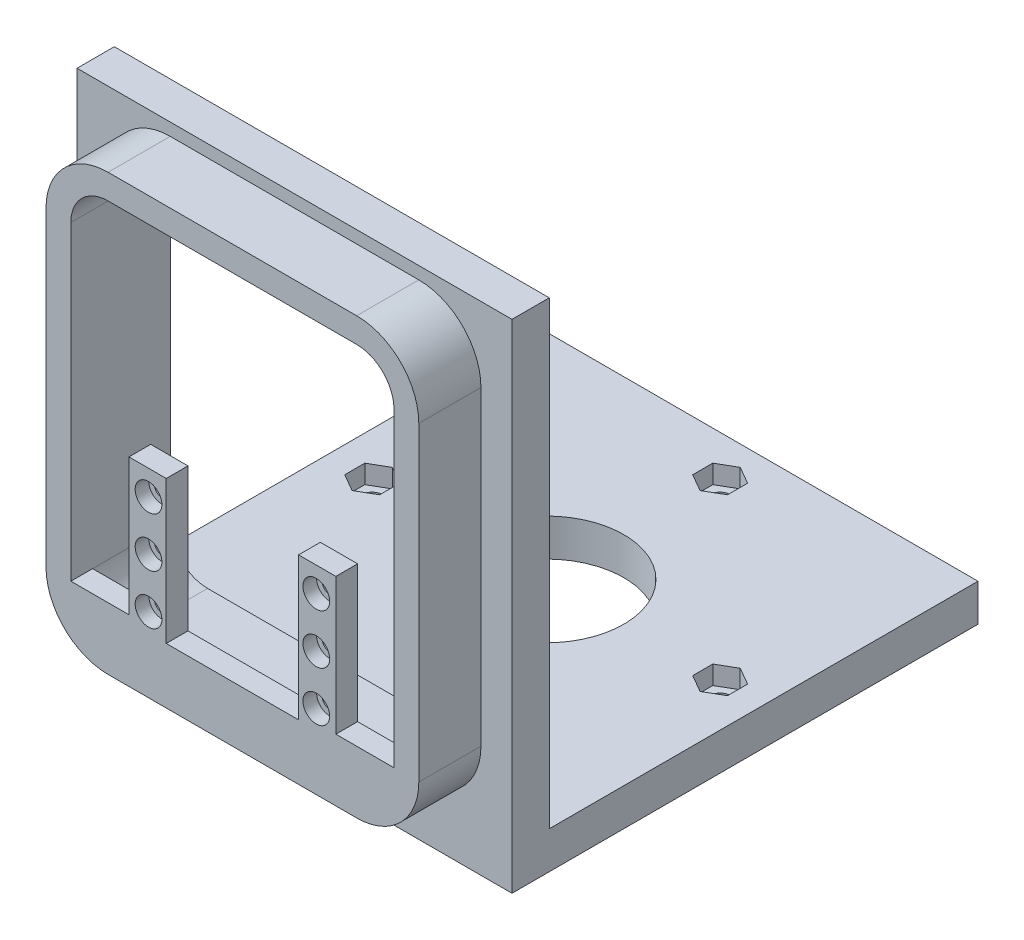
SolidWorks part; units mm, degrees
ref_plane "Front Plane" through (0, 0, 0) normal (0, 0, 1) x (1, 0, 0)
ref_plane "Top Plane" through (0, 0, 0) normal (0, 1, 0) x (1, 0, 0)
ref_plane "Right Plane" through (0, 0, 0) normal (1, 0, 0) x (0, 0, -1)
sketch "Sketch1" plane through (0, 0, 0) normal (0, 0, 1) x (1, 0, 0)
  line L1 (-20, -35) -> (20, -35)
  line L2 (-30, -25) -> (-30, 25)
  line L3 (-20, 35) -> (20, 35)
  line L4 (30, -25) -> (30, 25)
  line L5 (-30, -35) -> (30, 35) construction
  line L6 (-30, 35) -> (30, -35) construction
  arc A1 (20, 35) -> (30, 25) centre (20, 25) cw
  arc A2 (20, -35) -> (30, -25) centre (20, -25) ccw
  arc A3 (-20, -35) -> (-30, -25) centre (-20, -25) cw
  arc A4 (-30, 25) -> (-20, 35) centre (-20, 25) cw
  point P0 (0, 0)
  dimension "D1" = 60
  dimension "D3" = 10
  dimension "D2" = 70
extrude "Boss-Extrude1" add sketch "Sketch1" against normal blind 10
ref_plane "Plane1" through (60, 0, 0) normal (1, 0, 0) x (0, 0, -1)
ref_plane "Plane2" through (60, 0, 0) normal (1, 0, 0) x (0, 0, -1)
sketch "Sketch10" plane through (0, 0, -10) normal (0, 0, -1) x (-1, 0, 0)
  line L0 (0, -3) -> (0, 0) construction
  line L1 (-35, -43) -> (35, -43)
  line L2 (-35, -43) -> (-35, 37)
  line L3 (-35, 37) -> (35, 37)
  line L4 (35, -43) -> (35, 37)
  line L5 (-35, -43) -> (35, 37) construction
  line L6 (-35, 37) -> (35, -43) construction
  point P0 (0, -3)
  dimension "D3" = 3
  dimension "D1" = 80
  dimension "D2" = 70
extrude "Boss-Extrude6" add sketch "Sketch10" along normal blind 75
sketch "Sketch14" plane through (0, 0, 0) normal (0, 0, 1) x (1, 0, 0)
  line L8 (20, 31) -> (-20, 31)
  line L9 (26, -25) -> (26, 25)
  line L10 (-20, -31) -> (20, -31)
  line L11 (-26, 25) -> (-26, -25)
  line L12 (20, 31) -> (-20, 31)
  line L13 (26, -25) -> (26, 25)
  line L14 (-20, -31) -> (20, -31)
  line L15 (-26, 25) -> (-26, -25)
  arc A10 (26, 25) -> (20, 31) centre (20, 25) ccw
  arc A11 (20, -31) -> (26, -25) centre (20, -25) ccw
  arc A12 (-26, -25) -> (-20, -31) centre (-20, -25) ccw
  arc A13 (-20, 31) -> (-26, 25) centre (-20, 25) ccw
  arc A14 (26, 25) -> (20, 31) centre (20, 25) ccw
  arc A15 (20, -31) -> (26, -25) centre (20, -25) ccw
  arc A16 (-26, -25) -> (-20, -31) centre (-20, -25) ccw
  arc A17 (-20, 31) -> (-26, 25) centre (-20, 25) ccw
  dimension "D1" = 4
extrude "Cut-Extrude7" cut sketch "Sketch14" against normal blind 46
sketch "Sketch15" plane through (0, 0, 0) normal (0, 0, 1) x (1, 0, 0)
  line L0 (0, 0) -> (0, -17.9719) construction
  line L1 (-16.65, -3) -> (-10.65, -3)
  line L2 (-10.65, -3) -> (-10.65, -26)
  line L3 (-10.65, -26) -> (10.65, -26)
  line L4 (10.65, -26) -> (10.65, -3)
  line L5 (10.65, -3) -> (16.65, -3)
  line L6 (16.65, -3) -> (16.65, -25)
  line L8 (-16.65, -3) -> (-16.65, -25)
  line L10 (0, 0) -> (13.5, 0) construction
  line L11 (13.5, 0) -> (13.5, -7) construction
  line L12 (13.5, -7) -> (13.5, -15) construction
  line L13 (13.5, -15) -> (13.5, -23) construction
  line L14 (-20, -31) -> (20, -31) construction
  line L15 (-20, -31) -> (20, -31)
  line L16 (26, -25) -> (16.65, -25)
  line L17 (-26, -25) -> (-16.65, -25)
  circle A0 centre (0, 0) radius 11 construction
  circle A1 centre (13.5, -7) radius 1.25
  circle A3 centre (13.5, -15) radius 1.25
  circle A4 centre (13.5, -23) radius 1.25
  circle A5 centre (-13.5, -7) radius 1.25
  circle A6 centre (-13.5, -15) radius 1.25
  circle A7 centre (-13.5, -23) radius 1.25
  arc A9 (-26, -25) -> (-20, -31) centre (-20, -25) ccw
  arc A10 (26, -25) -> (20, -31) centre (20, -25) cw
  point P5 (0, -26)
  dimension "D1" = 22
  dimension "D5" = 2.5
  dimension "D2" = 21.3
  dimension "D3" = 13.5
  dimension "D4" = 7
  dimension "D6" = 8
  dimension "D7" = 8
  dimension "D8" = 6
  dimension "D9" = 5
  dimension "D10" = 3
extrude "Boss-Extrude7" add sketch "Sketch15" against normal blind 3.5
sketch "Sketch17" plane through (0, 0, 0) normal (0, 0, 1) x (1, 0, 0)
  circle A0 centre (-13.5, -7) radius 2.15
  circle A1 centre (-13.5, -15) radius 2.15
  circle A2 centre (-13.5, -23) radius 2.15
  circle A3 centre (13.5, -7) radius 2.15
  circle A4 centre (13.5, -15) radius 2.15
  circle A5 centre (13.5, -23) radius 2.15
  dimension "D1" = 4.3
extrude "Cut-Extrude9" cut sketch "Sketch17" against normal blind 2.2
sketch "Sketch19" plane through (35, 0, 0) normal (1, 0, 0) x (0, 0, -1)
  line L0 (85, -43) -> (10, -43) construction
  line L1 (85, 37) -> (16, 37)
  line L2 (85, 37) -> (85, -37)
  line L3 (85, -37) -> (16, -37)
  line L4 (16, 37) -> (16, -37)
  line L5 (10, 37) -> (10, -43) construction
  dimension "D1" = 6
  dimension "D2" = 6
extrude "Cut-Extrude11" cut sketch "Sketch19" against normal blind 70
sketch "Sketch20" plane through (0, -43, 0) normal (0, -1, 0) x (1, 0, 0)
  line L0 (-35, -16) -> (35, -85) construction
  line L1 (28, -50.5) -> (0, -50.5) construction
  circle A0 centre (28, -50.5) radius 1.65
  circle A1 centre (0, -78.5) radius 1.65
  circle A2 centre (-28, -50.5) radius 1.65
  circle A4 centre (0, -22.5) radius 1.65 [skipped]
  point P6 (0, -50.5)
  point P7 (0, 0)
  point P9 (0, 0)
  point P16 (0, -50.5)
  point P17 (-30.7969, -39.6436)
  point P18 (-33.0421, -37.4606)
  point P20 (0, 0)
  dimension "D1" = 3.3
  dimension "D3" = 28
  dimension "D2" = 4
extrude "Cut-Extrude12" cut sketch "Sketch20" against normal blind 10
sketch "Sketch21" plane through (0, -37, 0) normal (0, 1, 0) x (1, 0, 0)
  line L0 (-28, 50.5) -> (28, 50.5) construction
  circle A0 centre (0, 50.5) radius 12.5
  dimension "D1" = 25
extrude "Cut-Extrude13" cut sketch "Sketch21" against normal blind 10
fillet "Fillet2" [suppressed] radius 20
sketch "Sketch22" plane through (0, -37, 0) normal (0, 1, 0) x (1, 0, 0)
  line L1 (0, 81.7332) -> (-2.8, 80.1166)
  line L2 (-2.8, 80.1166) -> (-2.8, 76.8834)
  line L3 (-2.8, 76.8834) -> (0, 75.2668)
  line L4 (0, 75.2668) -> (2.8, 76.8834)
  line L5 (2.8, 76.8834) -> (2.8, 80.1166)
  line L6 (2.8, 80.1166) -> (0, 81.7332)
  line L7 (-30.8, 48.8834) -> (-28, 47.2668)
  line L8 (-28, 47.2668) -> (-25.2, 48.8834)
  line L9 (-25.2, 48.8834) -> (-25.2, 52.1166)
  line L10 (-25.2, 52.1166) -> (-28, 53.7332)
  line L11 (-28, 53.7332) -> (-30.8, 52.1166)
  line L12 (-30.8, 52.1166) -> (-30.8, 48.8834)
  line L19 (28, 53.7332) -> (25.2, 52.1166)
  line L20 (25.2, 52.1166) -> (25.2, 48.8834)
  line L21 (25.2, 48.8834) -> (28, 47.2668)
  line L22 (28, 47.2668) -> (30.8, 48.8834)
  line L23 (30.8, 48.8834) -> (30.8, 52.1166)
  line L24 (30.8, 52.1166) -> (28, 53.7332)
  circle A0 centre (0, 78.5) radius 2.8 construction
  circle A1 centre (-28, 50.5) radius 2.8 construction
  circle A3 centre (28, 50.5) radius 2.8 construction
  dimension "D1" = 5.6
extrude "Cut-Extrude14" cut sketch "Sketch22" against normal blind 3
